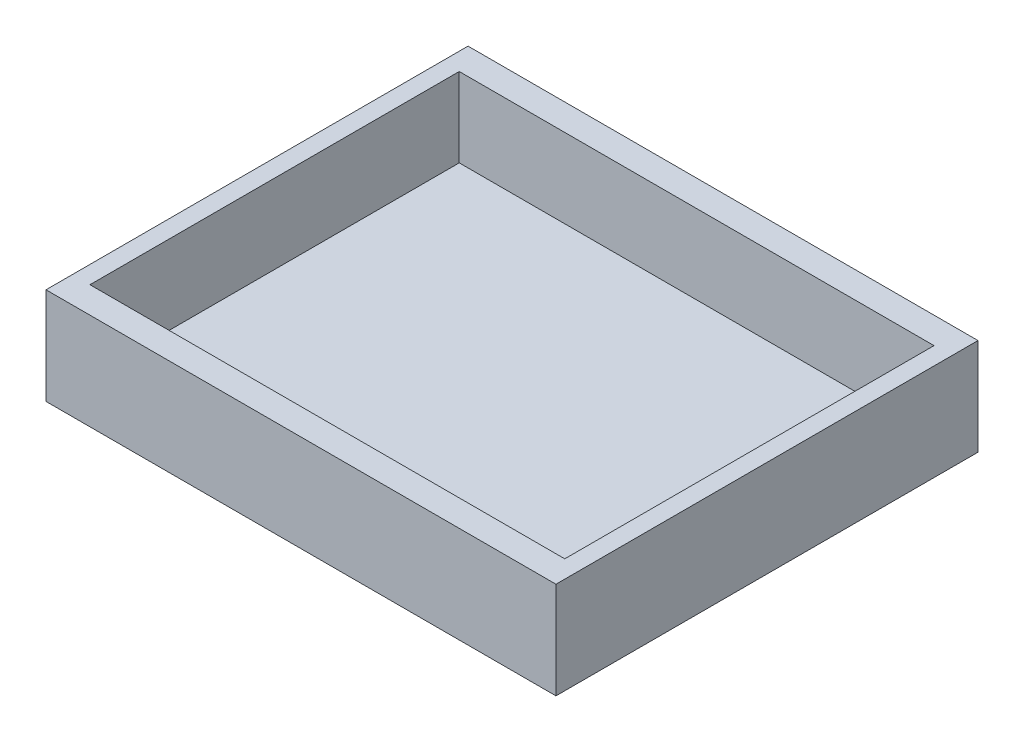
SolidWorks part; units mm, degrees
ref_plane "Front" through (0, 0, 0) normal (0, 0, 1) x (1, 0, 0)
ref_plane "Top" through (0, 0, 0) normal (0, 1, 0) x (1, 0, 0)
ref_plane "Right" through (0, 0, 0) normal (1, 0, 0) x (0, 0, -1)
sketch "Sketch1" plane through (0, 0, 0) normal (0, 1, 0) x (1, 0, 0)
  line L1 (-36.83, 30.48) -> (36.83, 30.48)
  line L2 (-36.83, 30.48) -> (-36.83, -30.48)
  line L3 (-36.83, -30.48) -> (36.83, -30.48)
  line L4 (36.83, 30.48) -> (36.83, -30.48)
  line L5 (-36.83, 30.48) -> (36.83, -30.48) construction
  line L6 (-36.83, -30.48) -> (36.83, 30.48) construction
  line L7 (-34.29, 26.67) -> (34.29, 26.67)
  line L8 (-34.29, 26.67) -> (-34.29, -26.67)
  line L9 (-34.29, -26.67) -> (34.29, -26.67)
  line L10 (34.29, 26.67) -> (34.29, -26.67)
  line L11 (-34.29, 26.67) -> (34.29, -26.67) construction
  line L12 (-34.29, -26.67) -> (34.29, 26.67) construction
  point P0 (0, 0)
  point P6 (0, 0)
  dimension "D1" = 60.96
  dimension "D2" = 73.66
  dimension "D3" = 53.34
  dimension "D4" = 68.58
extrude "pcb-base" add sketch "Sketch1" along normal blind 2.54 contours L8 L7 L10 L9
extrude "pcb-wall" add sketch "Sketch1<4>" along normal blind 13.97
sketch "Sketch1<4>" plane through (0, 0, 0) normal (0, 1, 0) x (1, 0, 0) same geometry as "Sketch1"
sketch "Sketch3" plane through (-36.83, 0, 0) normal (-1, 0, 0) x (0, 0, 1)
  line L0 (-30.48, 13.97) -> (-30.48, 0) construction
  line L1 (-30.48, 13.97) -> (30.48, 13.97) construction
  circle A0 centre (20.32, 4.318) radius 1.651
  dimension "D2" = 9.652
  dimension "D3" = 3.302
  dimension "D1" = 50.8
extrude "battery-gap" cut sketch "Sketch3" against normal up to vertex (2.54 mm away) contours A0 up to point (-34.29, 13.97, 26.67)
sketch "Sketch5" plane through (0, 0, 30.48) normal (0, 0, 1) x (1, 0, 0)
  circle A0 centre (-35.1498, 14.7751) radius 2.54
  point P2 (0, 0)
  point P3 (-35.1498, 14.7751)
  dimension "D1" = 5.08
